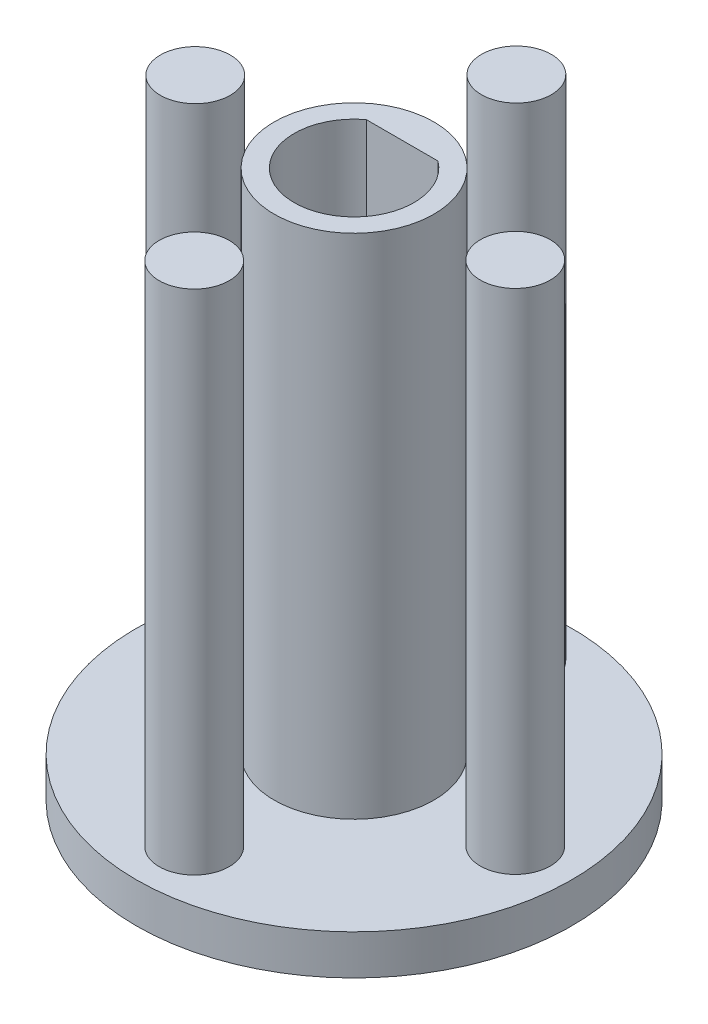
SolidWorks part; units mm, degrees
ref_plane "Front Plane" through (0, 0, 0) normal (0, 0, 1) x (1, 0, 0)
ref_plane "Top Plane" through (0, 0, 0) normal (0, 1, 0) x (1, 0, 0)
ref_plane "Right Plane" through (0, 0, 0) normal (1, 0, 0) x (0, 0, -1)
sketch "Sketch3" plane through (0, 0, 0) normal (0, 1, 0) x (1, 0, 0)
  line L0 (-7.9995, 0.0532) -> (0.009, 8.1156) construction
  line L1 (0.009, 8.1156) -> (8.0177, 0.0533) construction
  line L2 (8.0177, 0.0533) -> (0.0092, -8.0091) construction
  line L3 (0.0092, -8.0091) -> (-7.9995, 0.0532) construction
  line L7 (18.7783, 0.0532) -> (-25.5315, 0.0532) construction
  line L8 (9.7482, 0.0532) -> (10.8982, 0.0532)
  line L9 (-1.7932, 2.4051) -> (1.7932, 2.4051)
  line L11 (0.009, -13.1564) -> (0.009, 16.0208) construction
  circle A0 centre (0, 0) radius 10.9
  circle A1 centre (0.009, 8.1156) radius 1.75
  circle A2 centre (8.0177, 0.0533) radius 1.75
  circle A3 centre (0.0092, -8.0091) radius 1.75
  circle A4 centre (-7.9995, 0.0532) radius 1.75
  circle A5 centre (0, 0) radius 4
  arc A6 (-1.7932, 2.4051) -> (1.7932, 2.4051) centre (0, 0) ccw
  dimension "D1" = 21.8
extrude "Boss-Extrude3" add sketch "Sketch3" along normal blind 27.4 contours A4 | A3 | A2 | A1 | A6 L9 | A5
extrude "Boss-Extrude4" add sketch "Sketch3<19>" along normal blind 2 contours A0
sketch "Sketch3<19>" plane through (0, 0, 0) normal (0, 1, 0) x (1, 0, 0) same geometry as "Sketch3"
